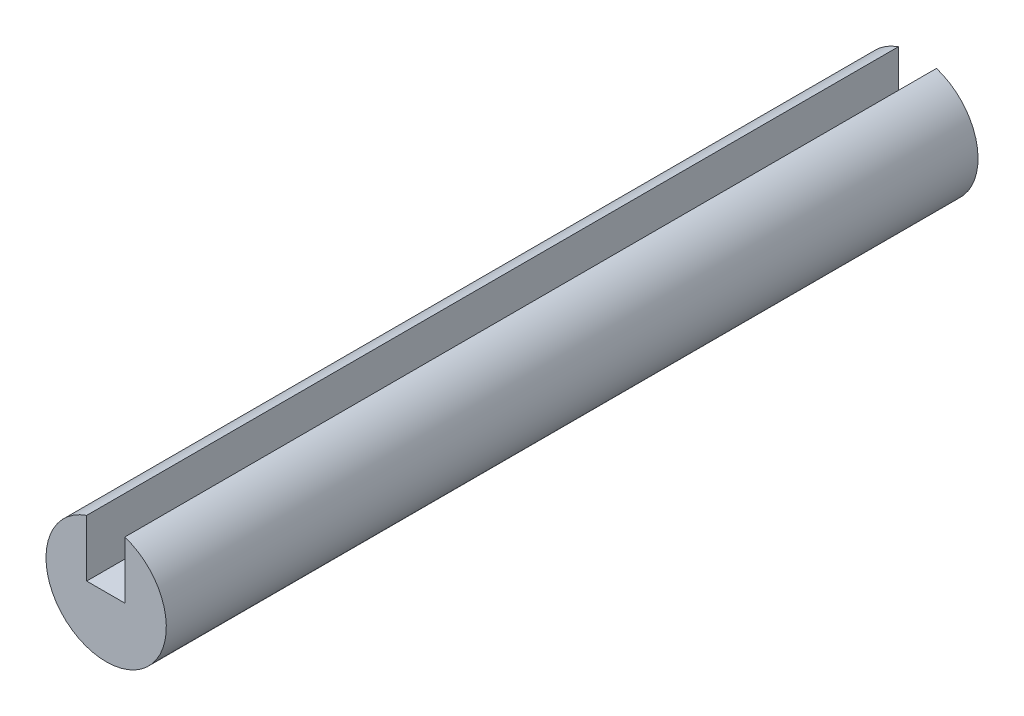
SolidWorks part; units mm, degrees
material "Alloy Steel"
ref_plane "Front Plane" through (0, 0, 0) normal (0, 0, 1) x (1, 0, 0)
ref_plane "Top Plane" through (0, 0, 0) normal (0, 1, 0) x (1, 0, 0)
ref_plane "Right Plane" through (0, 0, 0) normal (1, 0, 0) x (0, 0, -1)
sketch "Sketch1" plane through (0, 0, 0) normal (0, 0, 1) x (1, 0, 0)
  circle A0 centre (0, 0) radius 6.3
extrude "Boss-Extrude1" add sketch "Sketch1" along normal blind 80 and the other way blind 5
sketch "Sketch2" plane through (0, 0, 80) normal (0, 0, 1) x (1, 0, 0)
  line L0 (0, 0) -> (1.9501, 0)
  line L1 (1.9501, 0) -> (1.9501, 10.0041)
  line L2 (1.9501, 10.0041) -> (-2.0395, 10.0041)
  line L3 (-2.0395, 10.0041) -> (-2.0395, 0)
  line L4 (-2.0395, 0) -> (0, 0)
extrude "Cut-Extrude2" cut sketch "Sketch2" against normal blind 85
